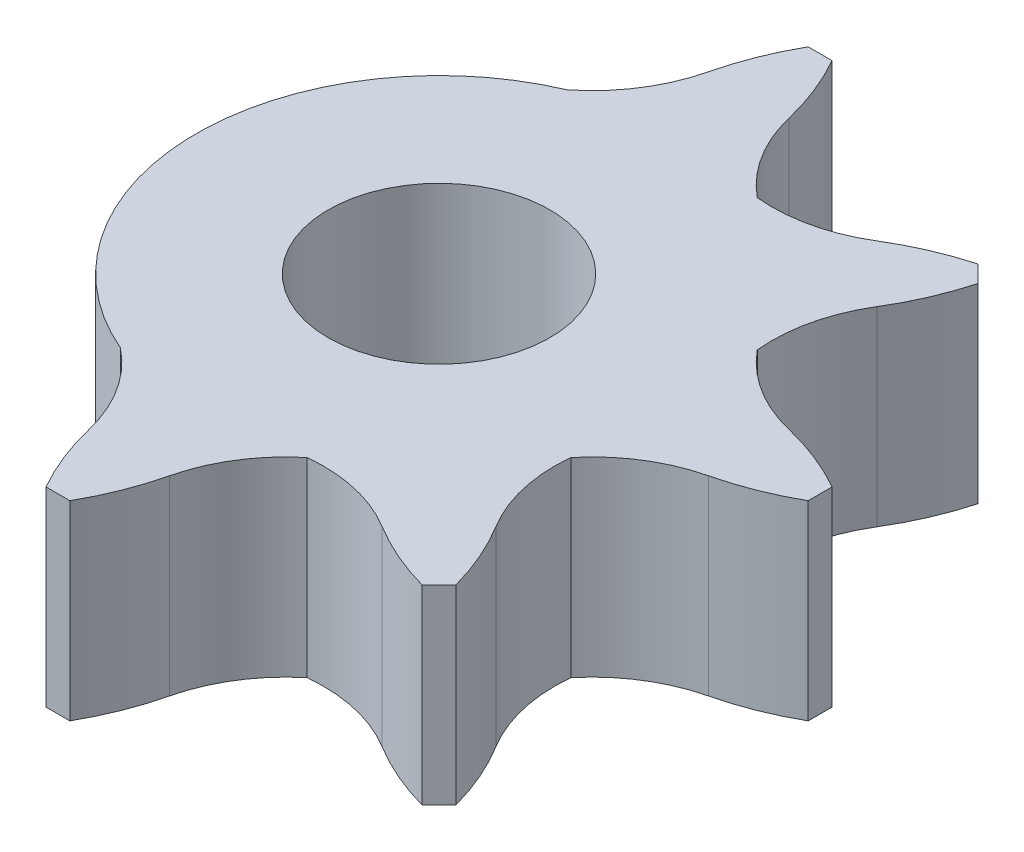
SolidWorks part; units mm, degrees
ref_plane "Front Plane" through (0, 0, 0) normal (0, 0, 1) x (1, 0, 0)
ref_plane "Top Plane" through (0, 0, 0) normal (0, 1, 0) x (1, 0, 0)
ref_plane "Right Plane" through (0, 0, 0) normal (1, 0, 0) x (0, 0, -1)
sketch "Sketch1" plane through (0, 0, 0) normal (0, 1, 0) x (1, 0, 0)
  line L2 (0.25, 7.9938) -> (-0.25, 7.9938)
  line L3 (-1, 4.9938) -> (1, 4.9938)
  line L4 (0, 7.9938) -> (0, 4.9938)
  line L6 (0, -2.325) -> (0, 2.325)
  line L7 (-0.8849, -2.15) -> (0.8849, -2.15)
  line L8 (0, 6.4938) -> (0.8439, 6.4938)
  line L9 (0, 6.4938) -> (-0.8439, 6.4938)
  line L10 (-2, 4.6838) -> (2, 4.6838)
  circle A0 centre (0, 0) radius 5.093
  arc A1 (-1, 4.9938) -> (-0.25, 7.9938) centre (4.7249, 5.1563) cw
  arc A2 (0.25, 7.9938) -> (1, 4.9938) centre (-4.7249, 5.1563) cw
  circle A3 centre (0, 0) radius 2.325
  arc A4 (-0.8439, 6.4938) -> (-2, 4.6838) centre (-4.0411, 7.2617) cw
  arc A5 (0.8439, 6.4938) -> (2, 4.6838) centre (4.0411, 7.2617) ccw
  dimension "D4" = 5.7272
  dimension "D5" = 10.1859
  dimension "D6" = 4.65
  dimension "D1" = 3
  dimension "D2" = 2
  dimension "D3" = 0.5
  dimension "D7" = 0.175
  dimension "D8" = 4
  dimension "D9" = 46.245
extrude "Boss-Extrude1" add sketch "Sketch1" along normal blind 4 contours A1 L2 A2 L3 | L10 A5 L8 L9 A4
sketch "Sketch4" plane through (0, 0, 0) normal (1, 0, 0) x (0, 0, -1)
  line L0 (0, 0) -> (0, 7.6311)
pattern_circular "CirPattern2" count 5 over 180 about axis through (0, 0, 0) along (0, 1, 0) of "Boss-Extrude1" reverse direction yes
extrude "Boss-Extrude3" add sketch "Sketch1<5>" along normal blind 4 contours L10 A0 A3 region at (4.1321, 0, -2.7286)
sketch "Sketch1<5>" plane through (0, 0, 0) normal (0, 1, 0) x (1, 0, 0) same geometry as "Sketch1"
equation "\"teeth\"= 10'num of teeth in gear"
equation "\"gearRadius\"= \"teeth\" * 4 / ( 2 * Pi )"
equation "\"D5@Sketch1\"=\"gearRadius\"*2"
equation "\"D1@CirPattern2\"=\"teeth\"/2"
equation "\"thickness\"= 4"
equation "\"D1@Boss-Extrude1\"=\"thickness\""
equation "\"D1@Boss-Extrude3\"=\"thickness\""
